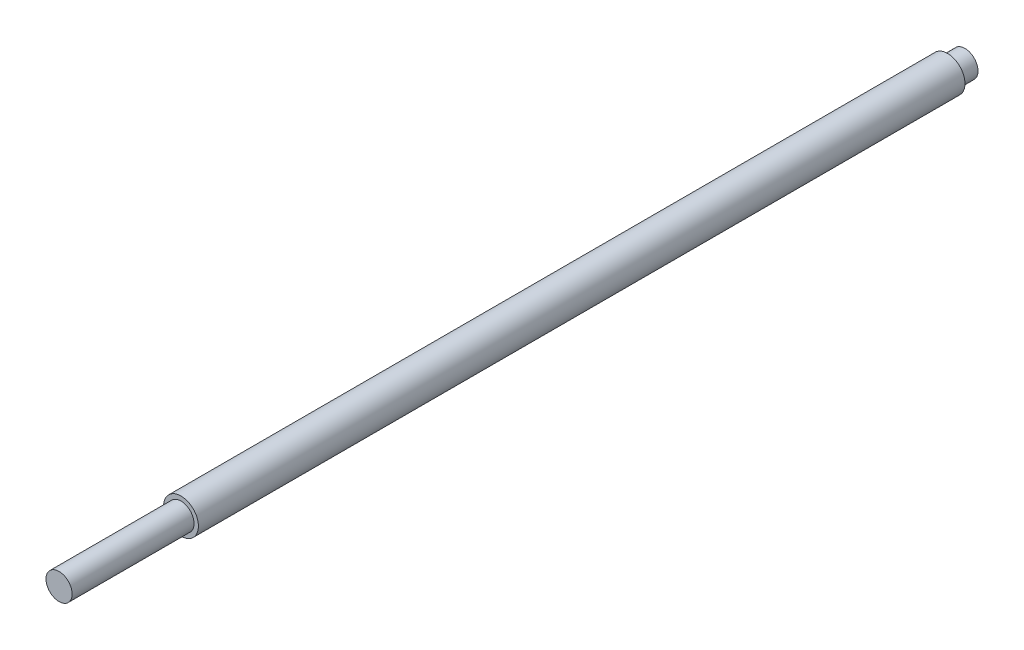
SolidWorks part; units mm, degrees
material "Plain Carbon Steel"
ref_plane "Front Plane" through (0, 0, 0) normal (0, 0, 1) x (1, 0, 0)
ref_plane "Top Plane" through (0, 0, 0) normal (0, 1, 0) x (1, 0, 0)
ref_plane "Right Plane" through (0, 0, 0) normal (1, 0, 0) x (0, 0, -1)
sketch "Sketch1" plane through (0, 0, 0) normal (0, 0, 1) x (1, 0, 0)
  circle A0 centre (0, 0) radius 6.35
  dimension "D1" = 12.7
extrude "Boss-Extrude1" add sketch "Sketch1" along normal blind 330.2 contours A0
sketch "Sketch2" plane through (0, 0, 330.2) normal (0, 0, 1) x (1, 0, 0)
  circle A0 centre (0, 0) radius 6.35
  circle A1 centre (0, 0) radius 4.7625
  circle A2 centre (0, 0) radius 6.35 construction
  dimension "D1" = 9.525
extrude "Cut-Extrude1" cut sketch "Sketch2" against normal blind 44.45
sketch "Sketch3" plane through (0, 0, 0) normal (0, 0, -1) x (-1, 0, 0)
  circle A0 centre (0, 0) radius 6.35
  circle A1 centre (0, 0) radius 4.7625
  circle A2 centre (0, 0) radius 6.35 construction
  dimension "D1" = 9.525
extrude "Cut-Extrude2" cut sketch "Sketch3" against normal blind 6.35
sketch "Sketch4" plane through (0, 0, 285.75) normal (0, 0, 1) x (1, 0, 0)
  circle A0 centre (0, 0) radius 5.08
curve "Helix/Spiral1" pitch 2.54 height 279.4 turns 110
sketch "Sketch5" plane through (0, 0, 0) normal (0, 1, 0) x (1, 0, 0)
  line L0 (-6.35, -285.75) -> (-6.35, -283.8231)
  line L1 (-6.35, -6.35) -> (-6.35, -285.75) construction
  line L2 (-6.35, -283.8231) -> (-5.08, -284.1516)
  line L3 (-5.08, -284.1516) -> (-5.08, -285.4216)
  line L4 (-5.08, -285.4216) -> (-6.35, -285.75)
  dimension "D1" = 29
  dimension "D2" = 1.27
  dimension "D3" = 1.27
sweep "Cut-Sweep1" [suppressed] cut profiles "Sketch5" path "Helix/Spiral1"
equation "\"dovetail-angle\" = 55"
equation "\"dovetail-stock-width\" = 5"
equation "\"dovetail-stock-height\" = 1.25"
equation "\"dovetail-depth\" = 0.5 * \"dovetail-stock-height\""
equation "\"dovetail-throat-width\" = \"dovetail-stock-width\" - (2 * \"dovetail-depth\")"
equation "\"delta-x\" = 6"
equation "\"delta-y\" = 3"
equation "\"delta-z\"= 2.5"
equation "\"gib-thickness\" = 0.25"
equation "\"x-slide-length\" = \"dovetail-stock-width\" + \"delta-x\""
equation "\"y-slide-length\" = \"dovetail-stock-width\" + \"delta-y\""
equation "\"dog-point-diam\" = .149"
equation "\"dog-point-length\" = .067"
equation "\"dovetail-double-height\" = 2 * \"dovetail-depth\" + 0.5"
equation "\"acme-major-diam\" = .5"
equation "\"acme-pitch-diam\" = 0.45"
equation "\"D1@Sketch1\"=\"acme-major-diam\""
equation "\"acme-minor-diam\" = 0.4"
equation "\"D1@Boss-Extrude1\"=\"x-screw-length\""
equation "\"acme-nut-od\" = 1.47"
equation "\"acme-nut-length\" = 1"
equation "\"acme-nut-trim-height\" = .75"
equation "\"screw-bearing-od\" = 0.5"
equation "\"screw-bearing-length\" = .25"
equation "\"screw-bearing-id\" = .375"
equation "\"end-plate-thickness\" = \"screw-bearing-length\""
equation "\"screw-add-length\" = 2 * \"end-plate-thickness\" + 1 + 0.5"
equation "\"x-screw-length\" = \"x-slide-length\" + \"screw-add-length\""
equation "\"y-screw-length\" = \"y-slide-length\" + \"screw-add-length\""
equation "\"D1@Sketch2\"=\"screw-bearing-id\""
equation "\"D1@Cut-Extrude1\"=\"screw-add-length\"-\"end-plate-thickness\""
equation "\"D1@Sketch3\"=\"screw-bearing-id\""
equation "\"D1@Cut-Extrude2\"=\"end-plate-thickness\""
equation "\"acme-nut-mount-hole-space-horz\" = 0.82"
equation "\"acme-nut-mount-hole-space-vert\" = 0.5 * \"acme-nut-length\""
